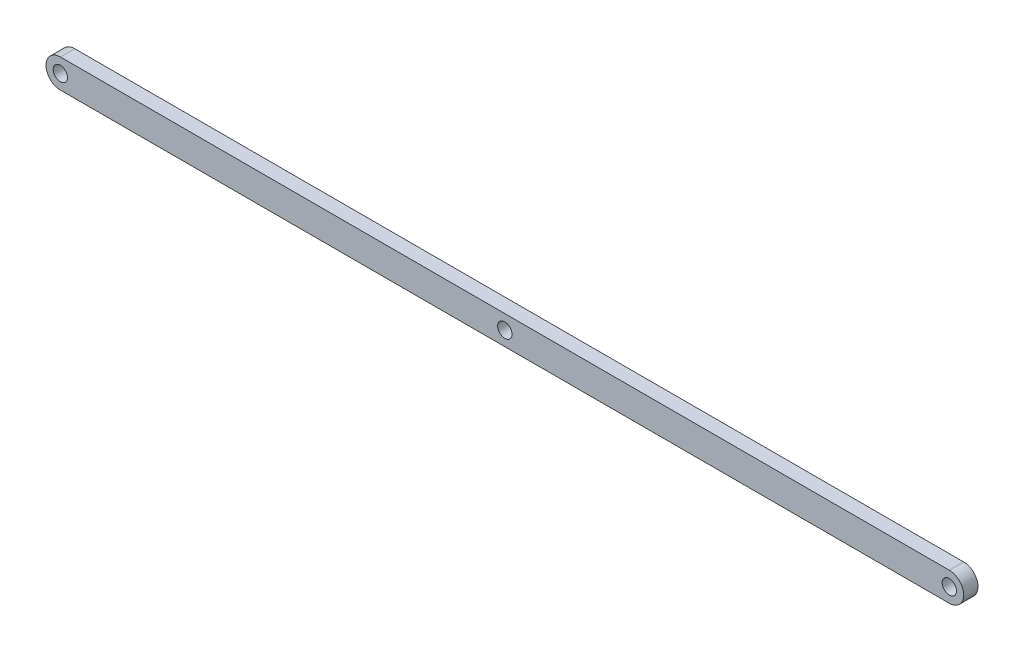
SolidWorks part; units mm, degrees
ref_plane "Front Plane" through (0, 0, 0) normal (0, 0, 1) x (1, 0, 0)
ref_plane "Top Plane" through (0, 0, 0) normal (0, 1, 0) x (1, 0, 0)
ref_plane "Right Plane" through (0, 0, 0) normal (1, 0, 0) x (0, 0, -1)
other "Center of Mass"
sketch "Sketch1" plane through (0, 0, 0) normal (0, 0, 1) x (1, 0, 0)
  line L0 (310, 0) -> (-310, 0) construction
  line L3 (310, -10) -> (-310, -10)
  line L4 (310, 10) -> (-310, 10)
  arc A5 (310, -10) -> (310, 10) centre (310, 0) ccw
  arc A6 (-310, 10) -> (-310, -10) centre (-310, 0) ccw
  circle A10 centre (-310, 0) radius 5
  circle A11 centre (310, 0) radius 5
  circle A12 centre (0, 0) radius 5
  point P3 (0, 0)
  point P4 (0, 0)
extrude "Boss-Extrude1" add sketch "Sketch1" along normal blind 10
